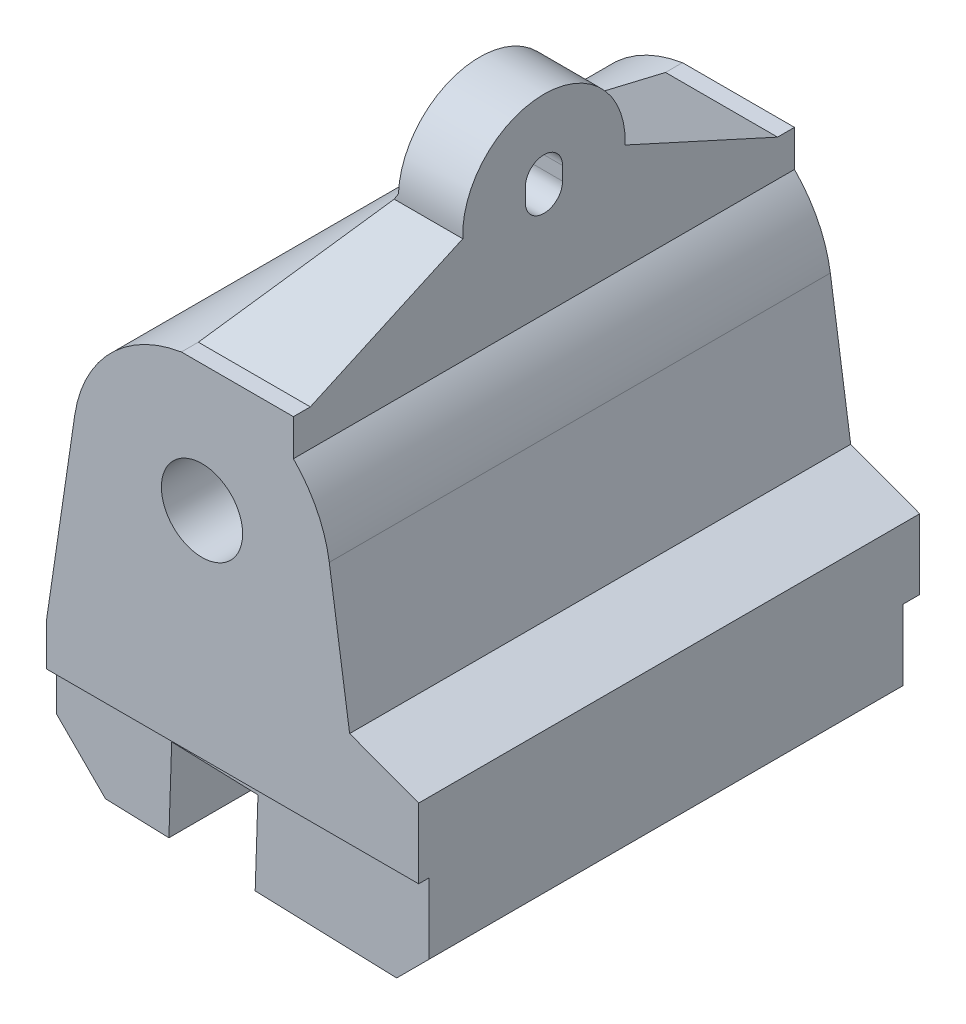
SolidWorks part; units mm, degrees
ref_plane "前视基准面" through (0, 0, 0) normal (0, 0, 1) x (1, 0, 0)
ref_plane "上视基准面" through (0, 0, 0) normal (0, 1, 0) x (1, 0, 0)
ref_plane "右视基准面" through (0, 0, 0) normal (1, 0, 0) x (0, 0, -1)
sketch "草图1" plane through (0, 0, 0) normal (0, 0, 1) x (1, 0, 0)
  line L0 (-92, -103) -> (-75.1879, 11.0805)
  line L1 (-92, -103) -> (-92, -153)
  line L2 (-92, -153) -> (-63, -182)
  line L3 (-63, -182) -> (-25.5545, -183.2345)
  line L4 (-25.5545, -183.2345) -> (-23.9079, -133.2846)
  line L5 (-23.9079, -133.2846) -> (27.0645, -134.965)
  line L6 (27.0645, -134.965) -> (25.4178, -184.9149)
  line L7 (25.4178, -184.9149) -> (109, -187.6703)
  line L8 (109, -187.6703) -> (128, -168.6703)
  line L9 (128, -168.6703) -> (128, -85.6703)
  line L10 (128, -85.6703) -> (32, -50) construction
  line L11 (75.1879, 11.0805) -> (92, -103) construction
  line L12 (0, 0) -> (0, -182) construction
  line L13 (-63, -182) -> (167.1773, -182) construction
  line L14 (-25.5545, -183.2345) -> (25.4178, -184.9149) construction
  line L15 (0, -182) -> (6, 0) construction
  line L16 (-63, -182) -> (-63, 0) construction
  line L17 (-63, -182) -> (-57, 0) construction
  line L18 (0, 0) -> (-116.977, 0) construction
  line L19 (0, 0) -> (32, 0) construction
  line L20 (0, -50) -> (32, -50) construction
  line L21 (0, -50) -> (-116.977, -50) construction
  line L22 (75.1879, 11.0805) -> (87.2127, -70.5152)
  line L23 (87.2127, -70.5152) -> (128, -85.6703)
  circle A0 centre (0, 0) radius 24 construction
  arc A1 (-58.5956, -48.4) -> (-57.2364, -50) centre (0, 0) ccw
  arc A2 (0, -76) -> (3.4972, -75.9195) centre (0, 0) ccw
  arc A3 (75.1879, 11.0805) -> (-76, 0) centre (0, 0) ccw
  point P16 (6, 0)
  point P20 (-0.0684, -182)
  point P33 (-0.0684, -184.0747)
  point P34 (0, -184.9149)
  dimension "D1" = 48
  dimension "D2" = 152
  dimension "D3" = 182
  dimension "D4" = 45
  dimension "D5" = 29
  dimension "D6" = 79
  dimension "D7" = 92
  dimension "D8" = 220
  dimension "D9" = 45
  dimension "D10" = 134
  dimension "D11" = 6
  dimension "D12" = 6
  dimension "D13" = 25.5
  dimension "D14" = 51
  dimension "D15" = 19
  dimension "D16" = 102
  dimension "D18" = 32
  dimension "D17" = 50
extrude "凸台-拉伸1" add sketch "草图1" along normal blind 296 contours L22 A3 L0 L1 L2 L3 L4 L5 L6 L7 L8 L9 L23 region at (10.9362, -66.0561, 0)
sketch "草图2" plane through (0, 0, 296) normal (0, 0, 1) x (1, 0, 0)
  circle A0 centre (0, 0) radius 24
  dimension "D1" = 48
extrude "切除-拉伸1" cut sketch "草图2" against normal up to next
sketch "草图3" plane through (0, 0, 296) normal (0, 0, 1) x (1, 0, 0)
  line L0 (54, 53.479) -> (54, 166)
  line L1 (54, 166) -> (16, 166)
  line L2 (16, 166) -> (16, 120)
  line L3 (16, 120) -> (-25, 54.5436) construction
  line L4 (16, 120) -> (-12.1751, 75.0184)
  arc A0 (75.1879, 11.0805) -> (-75.1879, 11.0805) centre (0, 0) ccw construction
  arc A1 (54, 53.479) -> (-12.1751, 75.0184) centre (0, 0) ccw
  circle A2 centre (0, 0) radius 60 construction
  dimension "D5" = 120
  dimension "D1" = 348
  dimension "D2" = 54
  dimension "D3" = 38
  dimension "D4" = 120
  dimension "D6" = 41
extrude "凸台-拉伸2" add sketch "草图3" against normal up to surface (296 mm away) up to face at (24, 0, 0)
sketch "草图4" plane through (16, 0, 0) normal (-1, 0, 0) x (0, 0, 1)
  line L0 (148, 166) -> (148, -244.5055) construction
  line L1 (0, 166) -> (296, 166) construction
  line L3 (296, 24) -> (0, 24) construction
  line L4 (296, 24) -> (0, 24) construction
  line L5 (0, -24) -> (296, -24) construction
  line L6 (0, -24) -> (296, -24) construction
  line L7 (247.7162, 24) -> (247.7162, -24) construction
  line L8 (247.7162, 0) -> (364.965, 0) construction
  line L9 (148, 124) -> (148, 116) construction
  line L10 (159, 124) -> (159, 116)
  line L11 (137, 124) -> (137, 116)
  line L12 (0, 120) -> (296, 120) construction
  arc A0 (159, 124) -> (137, 124) centre (148, 124) ccw
  arc A1 (137, 116) -> (159, 116) centre (148, 116) ccw
  point P15 (148, 120)
  dimension "D1" = 11
  dimension "D2" = 30
extrude "切除-拉伸2" cut sketch "草图4" against normal up to next and the other way up to next
sketch "草图5" plane through (16, 0, 0) normal (-1, 0, 0) x (0, 0, 1)
  line L0 (137, 120) -> (159, 120) construction
  circle A0 centre (148, 120) radius 38
  dimension "D1" = 76
extrude "切除-拉伸4" cut sketch "草图5" against normal blind 16 and the other way up to next
sketch "草图6" plane through (16, 0, 0) normal (-1, 0, 0) x (0, 0, 1)
  line L0 (296, 75.0184) -> (286, 75.0184)
  line L1 (0, 75.0184) -> (296, 75.0184) construction
  line L2 (286, 75.0184) -> (195.9583, 116)
  line L3 (100.0417, 116) -> (10, 75.0184)
  line L4 (10, 75.0184) -> (0, 75.0184)
  line L6 (0, -24) -> (296, -24) construction
  line L7 (0, -24) -> (296, -24) construction
  line L8 (296, 24) -> (0, 24) construction
  line L9 (296, 24) -> (0, 24) construction
  line L10 (148, 24) -> (148, -24) construction
  line L11 (148, 0) -> (407.4993, 0) construction
  line L12 (0, 166) -> (296, 166) construction
  line L14 (0, 75.0184) -> (0, 166)
  line L15 (0, 166) -> (148, 166)
  line L16 (148, 166) -> (296, 166)
  line L17 (296, 166) -> (296, 75.0184)
  arc A1 (195.9583, 116) -> (100.0417, 116) centre (148, 118) ccw
  line M11 (0, 120) -> (110, 120)
  line M13 (186, 120) -> (296, 120)
  line M14 (296, 120) -> (296, 166)
  line M15 (296, 166) -> (0, 166)
  line M16 (0, 166) -> (0, 120)
  dimension "D4" = 96
  dimension "D1" = 10
  dimension "D2" = 10
  dimension "D3" = 116
extrude "切除-拉伸10" cut sketch "草图6" against normal up to next contours A1 M13 M14 M15 region at (16, 144.1918, 240.1069)
extrude "切除-拉伸11" cut sketch "草图6<5>" against normal up to next contours A1 M15 M16 M11 region at (16, 144.1918, 55.8931)
sketch "草图6<5>" plane through (16, 0, 0) normal (-1, 0, 0) x (0, 0, 1) same geometry as "草图6"
extrude "切除-拉伸12" cut sketch "草图6<6>" against normal up to next and the other way up to next contours A1 L14 L4 L3 M11 | A1 L2 L0 L17 M13 region at (16, 103.645, 259.8851) region at (16, 103.645, 36.1149)
sketch "草图6<6>" plane through (16, 0, 0) normal (-1, 0, 0) x (0, 0, 1) same geometry as "草图6"
sketch "草图10" plane through (0, 0, 296) normal (0, 0, 1) x (1, 0, 0)
  line L0 (-141.0758, -127) -> (212.4784, -127)
  dimension "D1" = 127
extrude "切除-拉伸-薄壁1" cut sketch "草图10" against normal blind 6 and the other way through all flip side to cut thin thin type one direction wall 70
sketch "草图11" plane through (0, 0, 0) normal (0, 0, -1) x (-1, 0, 0)
  line L0 (-166.219, -127) -> (149.1003, -127)
  dimension "D1" = 127
extrude "切除-拉伸-薄壁2" cut sketch "草图11" against normal blind 10 and the other way through all thin thin type one direction wall 70
sketch "草图12" plane through (-6.0619, -183.8771, 0) normal (-0.0329, -0.9995, 0) x (0.9995, -0.0329, 0)
  line L0 (31.4967, 10) -> (115.1244, 10) construction
  line L1 (31.4967, 290) -> (-19.5033, 290) construction
  line L2 (31.4967, 262.5) -> (87.8436, 79.6571)
  line L3 (31.4967, 290) -> (31.4967, 10) construction
  line L4 (31.4967, 85.9319) -> (38.1498, 64.3429)
  line L5 (31.4967, 290) -> (31.4967, 10) construction
  line L6 (5.9967, 290) -> (5.9967, 10) construction
  line L7 (-19.5033, 10) -> (31.4967, 10) construction
  line L9 (31.4967, 262.5) -> (31.4967, 85.9319)
  arc A0 (38.1498, 64.3429) -> (87.8436, 79.6571) centre (62.9967, 72) ccw
  point P6 (5.9967, 290)
  dimension "D3" = 52
  dimension "D1" = 62
  dimension "D2" = 57
  dimension "D4" = 190.5
extrude "切除-拉伸13" cut sketch "草图12" against normal up to surface (49.977 mm away) up to face at (1.5783, -134.1248, 150)
